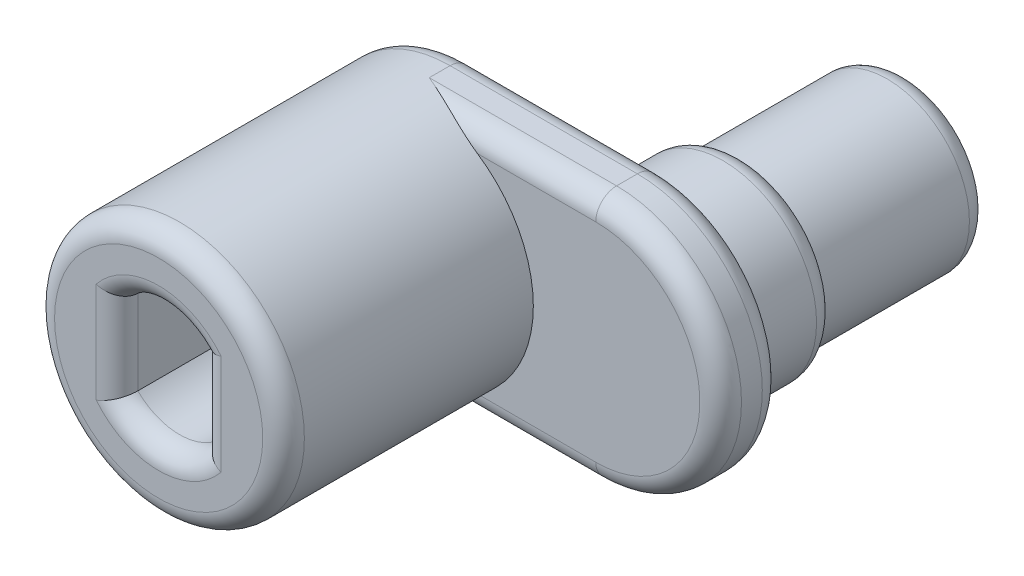
SolidWorks part; units mm, degrees
note: The reader was unsure of these and kept them because the rebuilt part matched: shared geometry of "Sketch1<3>", "Sketch1<6>", "Sketch1<7>", "Sketch1<12>".
ref_plane "Front Plane" through (0, 0, 0) normal (0, 0, 1) x (1, 0, 0)
ref_plane "Top Plane" through (0, 0, 0) normal (0, 1, 0) x (1, 0, 0)
ref_plane "Right Plane" through (0, 0, 0) normal (1, 0, 0) x (0, 0, -1)
sketch "Sketch1" plane through (0, 0, 0) normal (0, 0, 1) x (1, 0, 0)
  line L0 (0, 0) -> (0, 6) construction
  line L1 (0, 6) -> (-9, 6)
  line L2 (-9, 6) -> (-9, -6) construction
  line L3 (-9, -6) -> (0, -6)
  line L4 (0, -6) -> (0, 0) construction
  line L5 (-10.85, -1.9666) -> (-10.85, 1.9666) construction
  line L6 (-7.15, -1.9666) -> (-7.15, 1.9666) construction
  line L7 (-9, 0) -> (-10.85, 0) construction
  line L8 (-9, 0) -> (-7.15, 0) construction
  line L10 (-7, -2.0304) -> (-7, 2.0304)
  line L11 (-11, -2.0304) -> (-11, 2.0304)
  circle A0 centre (0, 0) radius 4 construction
  circle A2 centre (-9, 0) radius 6
  circle A3 centre (0, 0) radius 3.95
  arc A4 (-10.85, -1.9666) -> (-7.15, -1.9666) centre (-9, 0) ccw construction
  arc A5 (-7.15, 1.9666) -> (-10.85, 1.9666) centre (-9, 0) ccw construction
  circle A6 centre (0, 0) radius 4.5
  arc A7 (0, -6) -> (0, 6) centre (0, 0) ccw
  arc A8 (-7, 2.0304) -> (-11, 2.0304) centre (-9, 0) ccw
  arc A9 (-11, -2.0304) -> (-7, -2.0304) centre (-9, 0) ccw
  dimension "D1" = 8
  dimension "D3" = 12
  dimension "D6" = 5.4
  dimension "D8" = 9
  dimension "D4" = 9
  dimension "D7" = 3.7
  dimension "D5" = 0.05
  dimension "D9" = 0.15
extrude "Boss-Extrude1" add sketch "Sketch1" along normal blind 3
extrude "Boss-Extrude2" add sketch "Sketch1<3>" against normal blind 12 contours A0 | A3
sketch "Sketch1<3>" plane through (0, 0, 0) normal (0, 0, 1) x (1, 0, 0) same geometry as "Sketch1"
extrude "Boss-Extrude4" add sketch "Sketch1<6>" along normal blind 15
sketch "Sketch1<6>" plane through (0, 0, 0) normal (0, 0, 1) x (1, 0, 0) same geometry as "Sketch1"
extrude "Boss-Extrude6" add sketch "Sketch1<7>" against normal blind 4 contours A2 A6 A3 | A2 A6 A3
sketch "Sketch1<7>" plane through (0, 0, 0) normal (0, 0, 1) x (1, 0, 0) same geometry as "Sketch1"
extrude "Boss-Extrude9" add sketch "Sketch1<12>" along normal blind 4 contours L11 A9 L10 A8
sketch "Sketch1<12>" plane through (0, 0, 0) normal (0, 0, 1) x (1, 0, 0) same geometry as "Sketch1"
fillet "Fillet1" radius 1 14 edges at (3.95, 0, -12) (-15, 0, 0) (-3, 0, 15) (-11, 0, 15) (-9, -2.85, 15) (-7, 0, 15) (-9, 2.85, 15) (4.5, 0, -4) (-4.5, -6, 0) (-4.5, -6, 3) (-4.5, 6, 0) (-4.5, 6, 3) (6, 0, 0) (6, 0, 3)
equation "\"1.5fmm\"=10"
